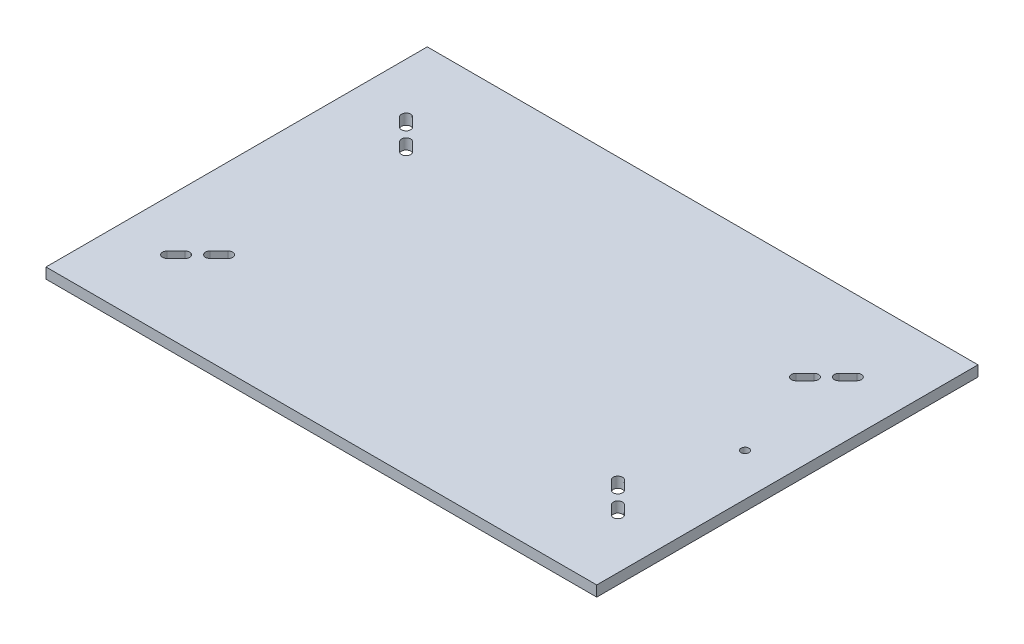
SolidWorks part; units mm, degrees
ref_plane "Front Plane" through (0, 0, 0) normal (0, 0, 1) x (1, 0, 0)
ref_plane "Top Plane" through (0, 0, 0) normal (0, 1, 0) x (1, 0, 0)
ref_plane "Right Plane" through (0, 0, 0) normal (1, 0, 0) x (0, 0, -1)
sketch "Sketch1" plane through (0, 0, 0) normal (0, 1, 0) x (1, 0, 0)
  line L1 (0, 0) -> (330.2, 0)
  line L2 (0, 0) -> (0, -228.6)
  line L3 (0, -228.6) -> (330.2, -228.6)
  line L4 (330.2, 0) -> (330.2, -228.6)
  dimension "D1" = 330.2
  dimension "D2" = 228.6
extrude "base plate" add sketch "Sketch1" against normal blind 6.35
sketch "center lines" plane through (0, 0, 0) normal (0, 1, 0) x (1, 0, 0)
  line L0 (165.1, 0) -> (165.1, -228.6) construction
  line L1 (330.2, 0) -> (0, 0) construction
  line L2 (0, -228.6) -> (330.2, -228.6) construction
  line L3 (0, -114.3) -> (330.2, -114.3) construction
  line L4 (0, 0) -> (0, -228.6) construction
  line L5 (330.2, -228.6) -> (330.2, 0) construction
sketch "Sketch3" plane through (0, 0, 0) normal (0, 1, 0) x (1, 0, 0)
  line L0 (21.0672, -185.8525) -> (30.0475, -194.8328)
  line L1 (30.0475, -194.8328) -> (60.5804, -164.2999)
  line L2 (60.5804, -164.2999) -> (51.6001, -155.3196)
  line L3 (51.6001, -155.3196) -> (21.0672, -185.8525)
  line L4 (29.9612, -185.9388) -> (35.3494, -180.5506) construction
  line L5 (28.0167, -183.9942) -> (33.4048, -178.6061)
  line L6 (31.9058, -187.8833) -> (37.2939, -182.4952)
  line L7 (0, -228.6) -> (330.2, -228.6) construction
  line L8 (48.2187, -167.6813) -> (42.8306, -173.0694) construction
  line L9 (50.1633, -169.6258) -> (44.7751, -175.014)
  line L10 (165.1, 0) -> (165.1, -228.6) construction
  line L11 (0, -114.3) -> (330.2, -114.3) construction
  line L12 (60.5804, -64.3001) -> (51.6001, -73.2804)
  line L13 (30.0475, -33.7672) -> (60.5804, -64.3001)
  line L14 (21.0672, -42.7475) -> (30.0475, -33.7672)
  line L15 (51.6001, -73.2804) -> (21.0672, -42.7475)
  line L16 (300.1525, -33.7672) -> (269.6196, -64.3001)
  line L17 (309.1328, -42.7475) -> (300.1525, -33.7672)
  line L18 (278.5999, -73.2804) -> (309.1328, -42.7475)
  line L19 (269.6196, -64.3001) -> (278.5999, -73.2804)
  line L20 (269.6196, -164.2999) -> (278.5999, -155.3196)
  line L21 (300.1525, -194.8328) -> (269.6196, -164.2999)
  line L22 (309.1328, -185.8525) -> (300.1525, -194.8328)
  line L23 (278.5999, -155.3196) -> (309.1328, -185.8525)
  line L24 (46.2742, -165.7367) -> (40.886, -171.1249)
  line L25 (29.9612, -42.6612) -> (35.3494, -48.0494) construction
  line L26 (28.0167, -44.6058) -> (33.4048, -49.9939)
  line L27 (31.9058, -40.7167) -> (37.2939, -46.1048)
  line L28 (48.2187, -60.9187) -> (42.8306, -55.5306) construction
  line L29 (50.1633, -58.9742) -> (44.7751, -53.586)
  line L30 (46.2742, -62.8633) -> (40.886, -57.4751)
  line L31 (300.2388, -42.6612) -> (294.8506, -48.0494) construction
  line L32 (302.1833, -44.6058) -> (296.7952, -49.9939)
  line L33 (298.2942, -40.7167) -> (292.9061, -46.1048)
  line L34 (281.9813, -60.9187) -> (287.3694, -55.5306) construction
  line L35 (280.0367, -58.9742) -> (285.4249, -53.586)
  line L36 (283.9258, -62.8633) -> (289.314, -57.4751)
  line L37 (281.9813, -167.6813) -> (287.3694, -173.0694) construction
  line L38 (280.0367, -169.6258) -> (285.4249, -175.014)
  line L39 (283.9258, -165.7367) -> (289.314, -171.1249)
  line L40 (300.2388, -185.9388) -> (294.8506, -180.5506) construction
  line L41 (302.1833, -183.9942) -> (296.7952, -178.6061)
  line L42 (298.2942, -187.8833) -> (292.9061, -182.4952)
  line L43 (51.6001, -164.2999) -> (51.6001, -155.3196)
  line L44 (60.5804, -164.2999) -> (51.6001, -164.2999)
  line L45 (51.6001, -64.3001) -> (51.6001, -73.2804)
  line L46 (60.5804, -64.3001) -> (51.6001, -64.3001)
  line L47 (278.5999, -64.3001) -> (278.5999, -73.2804)
  line L48 (269.6196, -64.3001) -> (278.5999, -64.3001)
  line L49 (278.5999, -164.2999) -> (278.5999, -155.3196)
  line L50 (269.6196, -164.2999) -> (278.5999, -164.2999)
  arc A0 (28.0167, -183.9942) -> (31.9058, -187.8833) centre (29.9612, -185.9388) ccw
  arc A1 (37.2939, -182.4952) -> (33.4048, -178.6061) centre (35.3494, -180.5506) ccw
  arc A2 (50.1633, -169.6258) -> (46.2742, -165.7367) centre (48.2187, -167.6813) ccw
  arc A3 (40.886, -171.1249) -> (44.7751, -175.014) centre (42.8306, -173.0694) ccw
  arc A4 (28.0167, -44.6058) -> (31.9058, -40.7167) centre (29.9612, -42.6612) cw
  arc A5 (37.2939, -46.1048) -> (33.4048, -49.9939) centre (35.3494, -48.0494) cw
  arc A6 (50.1633, -58.9742) -> (46.2742, -62.8633) centre (48.2187, -60.9187) cw
  arc A7 (40.886, -57.4751) -> (44.7751, -53.586) centre (42.8306, -55.5306) cw
  arc A8 (302.1833, -44.6058) -> (298.2942, -40.7167) centre (300.2388, -42.6612) ccw
  arc A9 (292.9061, -46.1048) -> (296.7952, -49.9939) centre (294.8506, -48.0494) ccw
  arc A10 (280.0367, -58.9742) -> (283.9258, -62.8633) centre (281.9813, -60.9187) ccw
  arc A11 (289.314, -57.4751) -> (285.4249, -53.586) centre (287.3694, -55.5306) ccw
  arc A12 (280.0367, -169.6258) -> (283.9258, -165.7367) centre (281.9813, -167.6813) cw
  arc A13 (289.314, -171.1249) -> (285.4249, -175.014) centre (287.3694, -173.0694) cw
  arc A14 (302.1833, -183.9942) -> (298.2942, -187.8833) centre (300.2388, -185.9388) cw
  arc A15 (292.9061, -182.4952) -> (296.7952, -178.6061) centre (294.8506, -180.5506) cw
  point P29 (32.6553, -183.2447)
  point P36 (45.5246, -170.3754)
  point P44 (32.6553, -45.3553)
  point P51 (45.5246, -58.2246)
  point P58 (297.5447, -45.3553)
  point P65 (284.6754, -58.2246)
  point P72 (284.6754, -170.3754)
  point P79 (297.5447, -183.2447)
  point P84 (37.2939, -178.6061)
  point P85 (40.886, -175.014)
  dimension "D6" = 2.75
  dimension "D10" = 5.08
  dimension "D9" = 2.032
  dimension "D1" = 43.18
  dimension "D2" = 12.7
  dimension "D3" = 45
  dimension "D4" = 99.9998
  dimension "D5" = 226.9998
  dimension "D7" = 7.62
  dimension "D8" = 6.35
extrude "slots" cut sketch "Sketch3" against normal through all contours A5 L27 A4 L26 | L33 A9 L32 A8 | L36 A11 L35 A10 | A13 L39 A12 L38 | A15 L42 A14 L41 | L6 A1 L5 A0 | L24 A3 L9 A2 | L30 A7 L29 A6 region at (32.6553, 0, 45.3553) region at (297.5447, 0, 45.3553) region at (284.6754, 0, 58.2246) region at (284.6754, 0, 170.3754) region at (297.5447, 0, 183.2447)
sketch "location of ESD" plane through (0, 0, 0) normal (0, 1, 0) x (1, 0, 0)
  line L0 (330.2, -228.6) -> (330.2, 0) construction
  line L1 (330.2, 0) -> (0, 0) construction
  point P0 (304.8, -114.3)
  point P3 (330.2, -114.3)
  dimension "D1" = 25.4
  dimension "D2" = 114.3
hole_wizard "ESD connector hole" positions "Sketch6" profile "Sketch7" hole size "#6-32" standard "PEM® Inch" end condition through all
sketch "Sketch6" plane through (0, 0, 0) normal (0, 1, 0) x (1, 0, 0)
  point P0 (304.8, -114.3)
sketch "Sketch7" plane through (304.8, 0, 114.3) normal (1, 0, 0) x (0, 0, 1)
  line L0 (0, 0) -> (0, 6.35)
  line L1 (0, 6.35) -> (2.3812, 6.35)
  line L2 (2.3812, 6.35) -> (2.3812, 0)
  line L5 (2.3812, 0) -> (0, 0)
  line L11 (0, -6.35) -> (0, 107.95) construction
  dimension "Thru Hole Dia." = 4.7625
  dimension "Thru Hole Depth" = 6.35
